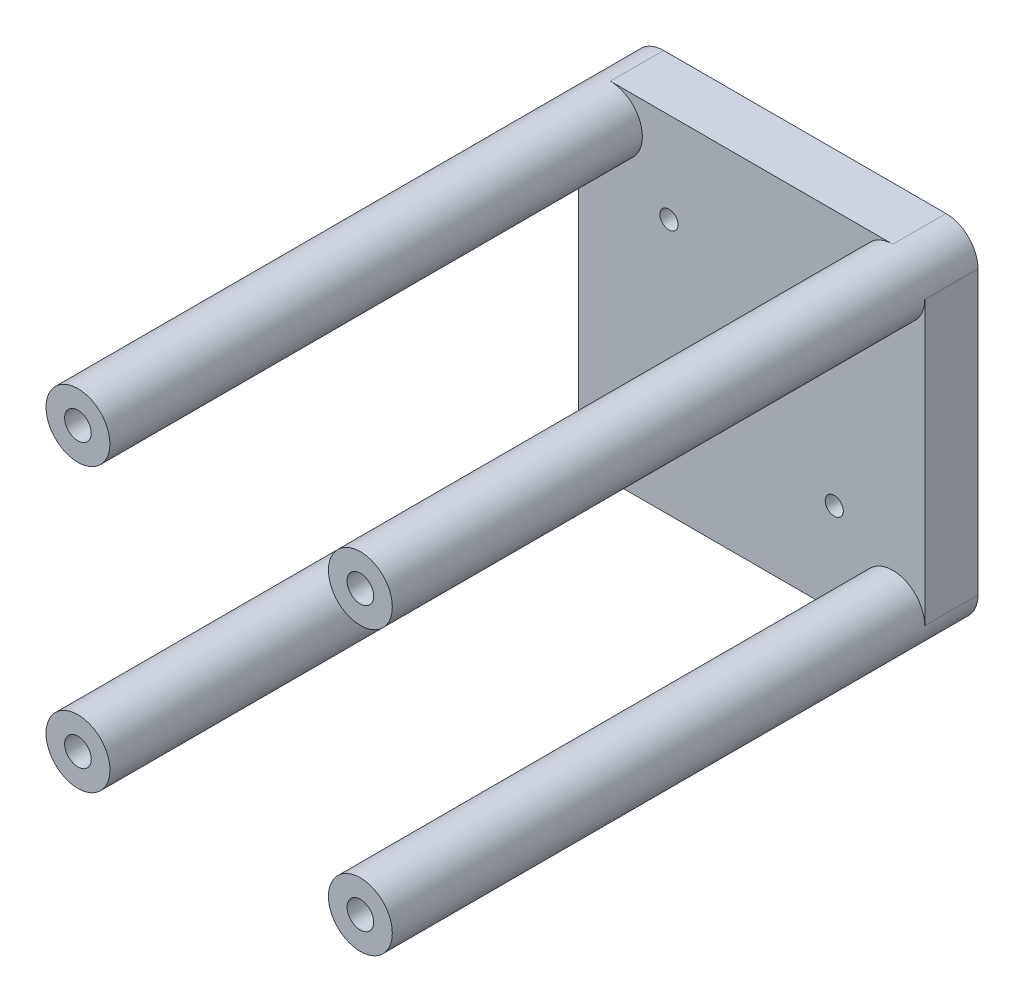
SolidWorks part; units mm, degrees
ref_plane "Piano frontale" through (0, 0, 0) normal (1, 0, 0) x (0, 1, 0)
ref_plane "Piano superiore" through (0, 0, 0) normal (0, 0, 1) x (0, 1, 0)
ref_plane "Piano destro" through (0, 0, 0) normal (0, 1, 0) x (-1, 0, 0)
sketch "Schizzo1" plane through (0, 0, 0) normal (0, 0, 1) x (0, 1, 0)
  line L1 (-32.52, -32.52) -> (32.52, -32.52)
  line L2 (-32.52, -32.52) -> (-32.52, 32.52)
  line L3 (-32.52, 32.52) -> (32.52, 32.52)
  line L4 (32.52, -32.52) -> (32.52, 32.52)
  line L5 (-32.52, -32.52) -> (32.52, 32.52) construction
  line L6 (-32.52, 32.52) -> (32.52, -32.52) construction
  point P0 (0, 0)
  point P10 (0, 0)
  dimension "D1" = 65.04
extrude "Estrusione-Estrusione2" add sketch "Schizzo1" along normal blind 10 contours L2 L3 L4 L1
fillet "Raccordo1" radius 6 4 edges at (32.52, -32.52, 5) (32.52, 32.52, 5) (-32.52, 32.52, 5) (-32.52, -32.52, 5)
hole_wizard "Foro per Vite M6-1" positions "Schizzo11" profile "Schizzo12" hole size "M6" standard "ISO"
sketch "Schizzo11" plane through (0, 0, 10) normal (0, 0, 1) x (1, 0, 0)
  point P0 (0, 0)
sketch "Schizzo12" plane through (0, 0, 10) normal (1, 0, 0) x (0, -1, 0)
  line L0 (0, 0) -> (0, 11.9828)
  line L1 (0, 11.9828) -> (3.3, 10)
  line L2 (3.3, 10) -> (3.3, 0)
  line L5 (3.3, 0) -> (0, 0)
  line L10 (0, 11.9828) -> (-3.3, 10) construction
  line L11 (0, -6.35) -> (0, 107.95) construction
  dimension "Hole Dia." = 6.6
  dimension "Hole Depth" = 10
  dimension "Drill Angle" = 118
hole_wizard "Foro per Vite M3-3" positions "Schizzo13" profile "Schizzo14" hole size "M3" standard "ISO"
sketch "Schizzo13" plane through (0, 0, 10) normal (0, 0, 1) x (1, 0, 0)
  line L1 (-15.52, -15.52) -> (15.52, -15.52)
  line L2 (-15.52, -15.52) -> (-15.52, 15.52)
  line L3 (-15.52, 15.52) -> (15.52, 15.52)
  line L4 (15.52, -15.52) -> (15.52, 15.52)
  line L5 (-15.52, -15.52) -> (15.52, 15.52) construction
  line L6 (-15.52, 15.52) -> (15.52, -15.52) construction
  point P1 (0, 0)
  point P2 (15.52, 15.52)
  point P5 (-15.52, -15.52)
  point P6 (-15.52, 15.52)
  point P7 (15.52, -15.52)
  dimension "D1" = 31.04
sketch "Schizzo14" plane through (0, 0, 10) normal (1, 0, 0) x (0, -1, 0)
  line L0 (0, 0) -> (0, 11.0215)
  line L1 (0, 11.0215) -> (1.7, 10)
  line L2 (1.7, 10) -> (1.7, 0)
  line L5 (1.7, 0) -> (0, 0)
  line L10 (0, 11.0215) -> (-1.7, 10) construction
  line L11 (0, -6.35) -> (0, 107.95) construction
  dimension "Hole Dia." = 3.4
  dimension "Hole Depth" = 10
  dimension "Drill Angle" = 118
sketch "Schizzo16" plane through (0, 0, 10) normal (0, 0, 1) x (1, 0, 0)
  circle A0 centre (-26.52, 26.52) radius 6
  arc A1 (-26.52, 32.52) -> (-32.52, 26.52) centre (-26.52, 26.52) ccw construction
  dimension "D1" = 12
extrude "Estrusione-Estrusione3" add sketch "Schizzo16" along normal blind 100
hole_wizard "Foro Ø0.15 (5)-1" positions "Schizzo17" profile "Schizzo18" hole size "Ø0.15" standard "ISO"
sketch "Schizzo17" plane through (0, 0, 110) normal (0, 0, 1) x (1, 0, 0)
  circle A0 centre (-26.52, 26.52) radius 6 construction
  point P0 (-26.52, 26.52)
sketch "Schizzo18" plane through (-26.52, 26.52, 110) normal (1, 0, 0) x (0, -1, 0)
  line L0 (0, 0) -> (0, 8)
  line L1 (0, 8) -> (2.5, 8)
  line L2 (2.5, 8) -> (2.5, 0)
  line L5 (2.5, 0) -> (0, 0)
  line L10 (0, 8) -> (-2.5, 8) construction
  line L11 (0, -6.35) -> (0, 107.95) construction
  dimension "Hole Dia." = 5
  dimension "Hole Depth" = 8
  dimension "Drill Angle" = 180
pattern_circular "RipetizioneCircolare3" count 4 over 360 about axis through (0, 0, 10) along (0, 0, 1) of "Estrusione-Estrusione3", "Foro Ø0.15 (5)-1"
